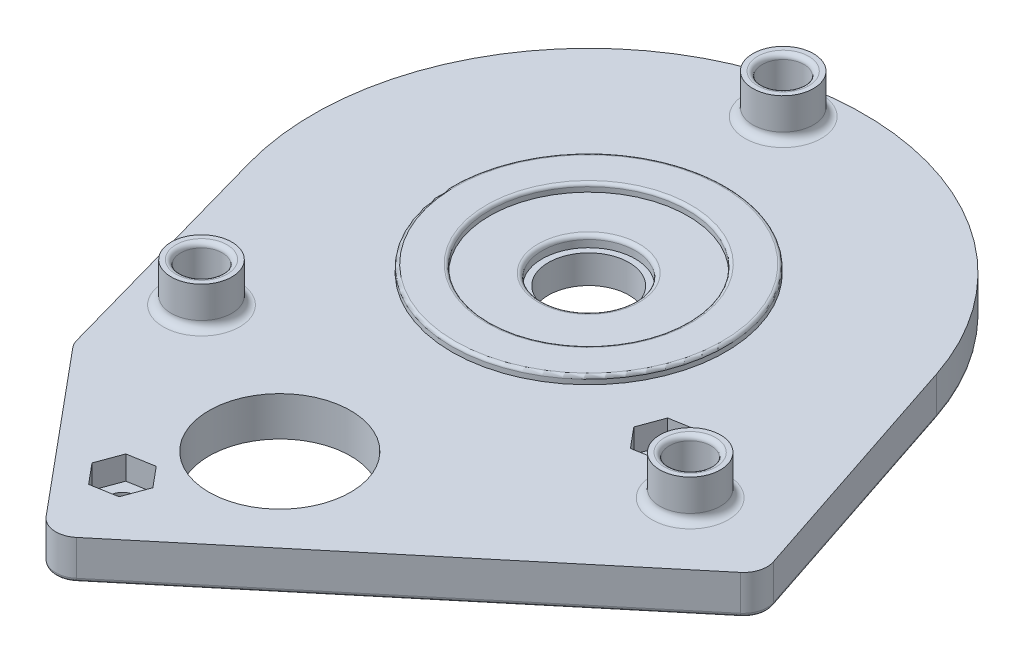
SolidWorks part; units mm, degrees
note: The reader was unsure of these and kept them because the rebuilt part matched: shared geometry of "Sketch1<3>", "Sketch1<4>", "Sketch1<6>", "Sketch1<7>", "Sketch2<3>".
ref_plane "Front Plane" through (0, 0, 0) normal (0, 0, 1) x (1, 0, 0)
ref_plane "Top Plane" through (0, 0, 0) normal (0, 1, 0) x (1, 0, 0)
ref_plane "Right Plane" through (0, 0, 0) normal (1, 0, 0) x (0, 0, -1)
sketch "Sketch1" plane through (0, 0, 0) normal (0, 1, 0) x (1, 0, 0)
  line L0 (0, -39.275) -> (0, 0) construction
  line L1 (-5.7681, -63.6005) -> (-24.9675, -40.5487)
  line L2 (-24.9675, -40.5487) -> (24.9779, 1.05)
  line L3 (24.9779, 1.05) -> (44.1773, -22.0018)
  line L4 (44.1773, -22.0018) -> (-5.7681, -63.6005)
  line L5 (-5.7142, -44.0343) -> (5.7142, -34.5157) construction
  line L6 (44.1773, -22.0018) -> (33.2189, 11.0229)
  line L7 (-24.9675, -40.5487) -> (-33.6967, -9.4621)
  line L8 (-5.2512, -42.1776) -> (-21.8799, -12.0942) construction
  line L9 (5.2512, -42.1776) -> (21.8799, -12.0942) construction
  line L10 (-21.1062, -28.1227) -> (-4.876, 29.6011) construction
  line L11 (-4.876, 29.6011) -> (31.1959, -18.2975) construction
  circle A0 centre (0, 0) radius 5.125
  circle A1 centre (0, 0) radius 5.925
  circle A2 centre (0, 0) radius 35
  circle A3 centre (0, 0) radius 25 construction
  circle A4 centre (0, 0) radius 12.6
  circle A5 centre (0, 0) radius 17.4
  circle A6 centre (0, -39.275) radius 9
  circle A7 centre (0, -39.275) radius 6 construction
  circle A8 centre (-21.1062, -28.1227) radius 1.6
  circle A9 centre (-21.1062, -28.1227) radius 3
  circle A10 centre (-21.1062, -28.1227) radius 7.0769 construction
  circle A11 centre (31.1959, -18.2975) radius 1.6
  circle A12 centre (31.1959, -18.2975) radius 3
  circle A13 centre (31.1959, -18.2975) radius 11.1542 construction
  circle A14 centre (-4.876, 29.6011) radius 5 construction
  circle A15 centre (-4.876, 29.6011) radius 3
  circle A16 centre (-4.876, 29.6011) radius 1.6
  point P18 (0, -39.275)
  dimension "D1" = 70
  dimension "D2" = 50
  dimension "D3" = 10.25
  dimension "D4" = 11.85
  dimension "D5" = 25.2
  dimension "D7" = 18
  dimension "D12" = 12
  dimension "D13" = 3.2
  dimension "D14" = 6
  dimension "D15" = 3.2
  dimension "D16" = 6
  dimension "D17" = 3.2
  dimension "D18" = 6
  dimension "D6" = 4.8
  dimension "D8" = 39.275
  dimension "D9" = 30
  dimension "D10" = 65
  dimension "D11" = 20
extrude "Boss-Extrude1" add sketch "Sketch1" along normal blind 5 contours A9 A2 L2 A5 L3 A15 | A15 A16 | L2 A5 A4 | A4 A1 | A1 A0 | L2 A5 | A12 A2 L3 L2 A5 A6 | A9 A2 L7 L2 | A12 A2 A6 L2 L1 L4 L3 | A2 L3 L6 | A2 A12 A11 | A2 A12 A11 | A2 A9 A8 | A2 A9 A8
extrude "Boss-Extrude2" add sketch "Sketch1<3>" along normal blind 1 from surface at 5 contours L2 A5 A4 | L2 A5 starting at face at (31.1959, 5, 19.8975)
sketch "Sketch1<3>" plane through (0, 0, 0) normal (0, 1, 0) x (1, 0, 0) same geometry as "Sketch1"
extrude "Cut-Extrude1" cut sketch "Sketch1<4>" along normal blind 3 contours A12 A11 | A9 A8 | A2 A12 A11 | A2 A9 A8 | A15 A16
sketch "Sketch1<4>" plane through (0, 0, 0) normal (0, 1, 0) x (1, 0, 0) same geometry as "Sketch1"
fillet "Fillet1" radius 3 3 edges at (44.1773, 2.5, 22.0018) (-5.7681, 2.5, 63.6005) (-24.9675, 2.5, 40.5487)
extrude "Cut-Extrude2" cut sketch "Sketch1<6>" against normal blind 1.4 from surface at 5 contours A1 A0 starting at face at (0, 5, 5.125)
sketch "Sketch1<6>" plane through (0, 0, 0) normal (0, 1, 0) x (1, 0, 0) same geometry as "Sketch1"
fillet "Fillet3" radius 0.5 1 edges at (0, 5, 5.925)
extrude "Boss-Extrude3" add sketch "Sketch1<7>" along normal blind 0.2 from surface at 3 contours A11 | A8 | A16 starting at face at (31.1959, 3, 19.8975)
sketch "Sketch1<7>" plane through (0, 0, 0) normal (0, 1, 0) x (1, 0, 0) same geometry as "Sketch1"
sketch "Sketch2" plane through (0, 0, 0) normal (0, -1, 0) x (1, 0, 0)
  line L0 (-7.6881, 61.2953) -> (-24.5576, 41.0409) construction
  line L1 (19.8177, 14.0831) -> (20.9745, 10.9407)
  line L2 (20.9745, 10.9407) -> (24.2743, 10.3713)
  line L3 (24.2743, 10.3713) -> (26.4174, 12.9443)
  line L4 (26.4174, 12.9443) -> (25.2606, 16.0868)
  line L5 (25.2606, 16.0868) -> (21.9607, 16.6562)
  line L6 (21.9607, 16.6562) -> (19.8177, 14.0831)
  line L7 (-10.6654, 52.4861) -> (-9.5085, 49.3436)
  line L8 (-9.5085, 49.3436) -> (-6.2087, 48.7742)
  line L9 (-6.2087, 48.7742) -> (-4.0656, 51.3473)
  line L10 (-4.0656, 51.3473) -> (-5.2224, 54.4897)
  line L11 (-5.2224, 54.4897) -> (-8.5223, 55.0592)
  line L12 (-8.5223, 55.0592) -> (-10.6654, 52.4861)
  arc A0 (-9.4621, 52.0361) -> (-7.8621, 53.9571) centre (-7.3655, 51.9167) ccw construction
  arc A1 (25.2141, 13.3943) -> (23.6142, 11.4733) centre (23.1175, 13.5137) ccw construction
  arc A2 (-9.4621, 52.0361) -> (-7.8621, 53.9571) centre (-7.3655, 51.9167) ccw
  arc A3 (25.2141, 13.3943) -> (23.6142, 11.4733) centre (23.1175, 13.5137) ccw
  circle A4 centre (-7.3655, 51.9167) radius 1.6
  circle A5 centre (23.1175, 13.5137) radius 1.6
  circle A6 centre (23.1175, 13.5137) radius 2.9 construction
  circle A7 centre (-7.3655, 51.9167) radius 2.9 construction
  dimension "D1" = 3.2
  dimension "D3" = 3.2
  dimension "D2" = 5.8
  dimension "D4" = 5.8
extrude "Cut-Extrude3" cut sketch "Sketch2" against normal through all contours A4 | A5
extrude "Cut-Extrude4" cut sketch "Sketch2<3>" along normal blind 3 from surface at -5 starting at face at (0, 5, 6.425)
sketch "Sketch2<3>" plane through (0, 0, 0) normal (0, -1, 0) x (1, 0, 0) same geometry as "Sketch2"
fillet "Fillet4" radius 0.5 8 edges at (-24.9077, 0, 40.5172) (-16.1228, 0, 51.1681) (-5.6553, 0, 62.363) (19.5714, 0, 42.4956) (43.5707, 0, 21.8287) (38.3761, 0, 4.5189) (-10.2453, 0, -33.4669) (-29.4187, 0, 24.6971)
fillet "Fillet5" radius 0.4 2 edges at (0, 6, 12.6) (0, 6, 17.4)
sketch "Sketch3" plane through (0, 5, 0) normal (0, 1, 0) x (1, 0, 0)
  circle A0 centre (31.1959, -18.2975) radius 1.6 construction
  circle A1 centre (-21.1062, -28.1227) radius 1.6 construction
  circle A2 centre (31.1959, -18.2975) radius 1.6
  circle A3 centre (-21.1062, -28.1227) radius 1.6
  circle A4 centre (-21.1062, -28.1227) radius 2.65
  circle A5 centre (-21.1062, -28.1227) radius 3.85
  circle A6 centre (31.1959, -18.2975) radius 2.65
  circle A7 centre (31.1959, -18.2975) radius 3.85
  circle A8 centre (-4.876, 29.6011) radius 1.6 construction
  circle A9 centre (-4.876, 29.6011) radius 1.6
  circle A10 centre (-4.876, 29.6011) radius 2.65
  circle A11 centre (-4.876, 29.6011) radius 3.85
  dimension "D1" = 5.3
  dimension "D3" = 5.3
  dimension "D6" = 5.3
  dimension "D2" = 1.2
  dimension "D5" = 1.2
extrude "Boss-Extrude4" add sketch "Sketch3" along normal blind 5 contours A7 A6 | A5 A4 | A11 A10
fillet "Fillet6" radius 0.6 3 edges at (-21.1062, 10, 30.7727) (31.1959, 10, 20.9475) (-4.876, 10, -26.9511)
fillet "Fillet7" radius 1 3 edges at (31.1959, 5, 22.1475) (-21.1062, 5, 31.9727) (-4.876, 5, -25.7511)
equation "\"M3Bolt\"=3.2"
equation "\"D13@Sketch1\"=\"M3Bolt\""
equation "\"M3Socket\"=6"
equation "\"D14@Sketch1\"=\"M3Socket\""
equation "\"D1@Sketch2\"=\"M3Bolt\""
equation "\"M3Nut\"=5.8"
equation "\"D2@Sketch2\"=\"M3Nut\""
equation "\"D3@Sketch2\"=\"M3Bolt\""
equation "\"D4@Sketch2\"=\"M3Nut\""
equation "\"D15@Sketch1\"=\"M3Bolt\""
equation "\"D16@Sketch1\"=\"M3Socket\""
equation "\"D3@Sketch3\"=\"D1@Sketch3\""
equation "\"D4@Sketch3\"=\"D2@Sketch3\""
equation "\"D17@Sketch1\"=\"M3Bolt\""
equation "\"D18@Sketch1\"=\"M3Socket\""
equation "\"D6@Sketch3\"=\"D1@Sketch3\""
equation "\"D5@Sketch3\"=\"D2@Sketch3\""
